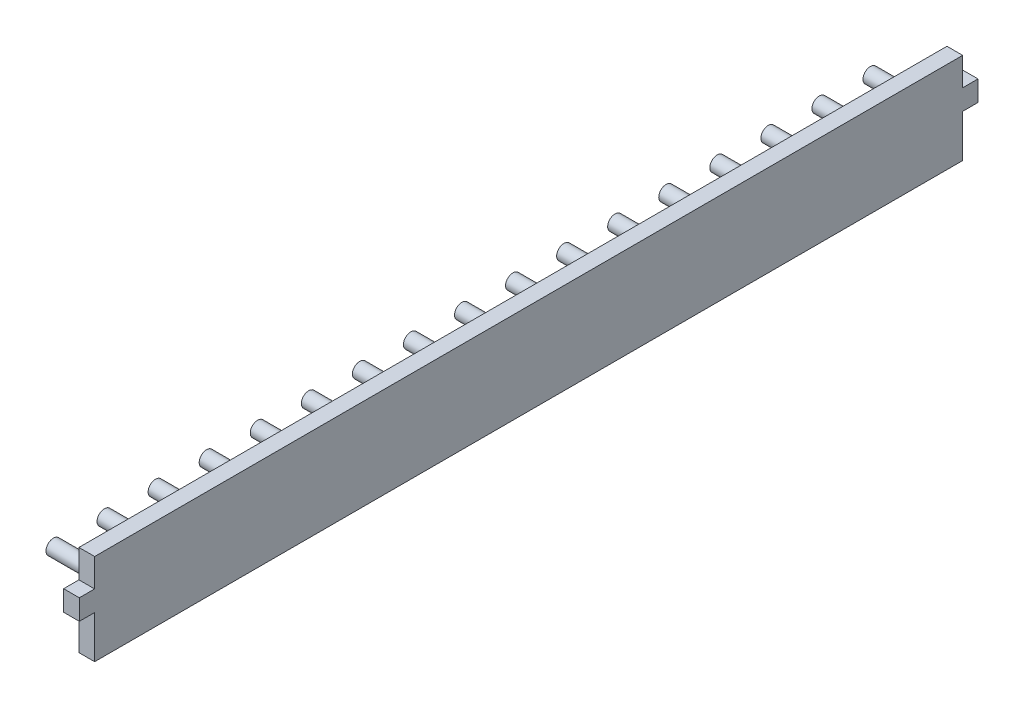
SolidWorks part; units mm, degrees
ref_plane "Front Plane" through (0, 0, 0) normal (0, 0, 1) x (1, 0, 0)
ref_plane "Top Plane" through (0, 0, 0) normal (0, 1, 0) x (1, 0, 0)
ref_plane "Right Plane" through (0, 0, 0) normal (1, 0, 0) x (0, 0, -1)
sketch "Sketch1" plane through (0, 0, 0) normal (0, 0, 1) x (1, 0, 0)
  line B0 (0, 7.95) -> (2.04, 7.95)
  line B1 (6.1524, 4.048) -> (6.1524, -4.048)
  line B2 (2.04, -7.95) -> (0, -7.95)
  line B3 (0, -7.95) -> (0, 7.95)
  line B4 (2.04, 7.95) -> (6.1524, 4.048)
  line B5 (6.1524, -4.048) -> (2.04, -7.95)
sketch_block_instance "Extrusion Profile-1"
sketch_block "Extrusion Profile" parameters "D1"=8.44, "D2"=2.6, "D3"=6, "D4"=16.7, "D6"=5.6686, "D7"=2.0404, "D8"=8.0963, "D9"=15.9, "D5"=2.4157
extrude "Boss-Extrude1" add sketch "Sketch1" along normal blind 340
sketch "Sketch2" plane through (0, 0, 0) normal (-1, 0, 0) x (0, 0, 1)
  circle A0 centre (10, 0) radius 2.9
  circle A1 centre (30, 0) radius 2.9
  circle A2 centre (50, 0) radius 2.9
  circle A3 centre (70, 0) radius 2.9
  circle A4 centre (90, 0) radius 2.9
  circle A5 centre (110, 0) radius 2.9
  circle A6 centre (130, 0) radius 2.9
  circle A7 centre (150, 0) radius 2.9
  circle A8 centre (170, 0) radius 2.9
  circle A9 centre (190, 0) radius 2.9
  circle A10 centre (210, 0) radius 2.9
  circle A11 centre (230, 0) radius 2.9
  circle A12 centre (250, 0) radius 2.9
  dimension "D2" = 5.8
  dimension "D1" = 10
  dimension "D4" = 20
  dimension "D3" = 13
extrude "Boss-Extrude2" add sketch "Sketch2" along normal blind 20
sketch "Sketch3" [suppressed] plane through (0, 0, 0) normal (-1, 0, 0) x (0, 0, 1)
  line L0 (190, 0) -> (210, 0) construction
  line L1 (200, 0) -> (200, 7.95) construction
  line L2 (260, 7.95) -> (0, 7.95) construction
  line L3 (200, 7.95) -> (200, 7)
  line L4 (200, 7) -> (100, 7)
  line L5 (100, 7) -> (100, 7.95)
  line L6 (100, 7.95) -> (200, 7.95)
  line L7 (90, 0) -> (110, 0) construction
  line L8 (100, 0) -> (100, 7) construction
  dimension "D1" = 7
extrude "Cut-Extrude1" [suppressed] cut sketch "Sketch3" against normal through all
chamfer "Chamfer1" [suppressed] distance 3 angle 45
fillet "Fillet1" [suppressed] radius 8
sketch "Sketch4" plane through (0, 0, 0) normal (-1, 0, 0) x (0, 0, 1)
  line L0 (250, 0) -> (230, 0) construction
  line L1 (250, 0) -> (270, 0) construction
  circle A0 centre (270, 0) radius 2.9
  circle A1 centre (250, 0) radius 2.9 construction
  circle A2 centre (290, 0) radius 2.9
  circle A3 centre (310, 0) radius 2.9
  circle A4 centre (330, 0) radius 2.9
  dimension "D2" = 20
  dimension "D1" = 4
extrude "Boss-Extrude3" add sketch "Sketch4" along normal blind 20
sketch "Sketch5" plane through (0, 0, 340) normal (0, 0, 1) x (1, 0, 0)
  line L5 (0, -7.95) -> (0, -20.95)
  line L6 (0, -20.95) -> (6.1524, -20.95)
  line L7 (6.1524, -20.95) -> (6.1524, -4.048)
  line L8 (0, -7.95) -> (2.04, -7.95) construction
  line L9 (0, -7.95) -> (2.04, -7.95)
  line L10 (2.04, -7.95) -> (6.1524, -4.048)
  line L11 (0, 7.95) -> (0, 14.75)
  line L12 (0, 14.75) -> (6.1524, 14.75)
  line L13 (6.1524, 14.75) -> (6.1524, 4.048)
  line L14 (2.04, 7.95) -> (0, 7.95) construction
  line L15 (0, 7.95) -> (2.04, 7.95)
  line L16 (2.04, 7.95) -> (6.1524, 4.048)
  dimension "D1" = 13
  dimension "D2" = 6.8
extrude "Boss-Extrude4" add sketch "Sketch5" against normal up to surface (340 mm away) up to face at (2.7308, 0, 0)
sketch "Sketch7" plane through (0, 0, 340) normal (0, 0, 1) x (1, 0, 0)
  line L0 (6.1524, -20.95) -> (6.1524, 14.75) construction
  line L1 (6.1524, -4.25) -> (0, -4.25)
  line L2 (6.1524, -4.25) -> (6.1524, 3.75)
  line L3 (6.1524, 3.75) -> (0, 3.75)
  line L4 (0, -4.25) -> (0, 3.75)
  line L5 (0, 14.75) -> (0, -20.95) construction
  line L6 (0, -0.25) -> (6.1524, -0.25)
  line L8 (6.1524, 14.75) -> (0, 14.75) construction
  line M7 (6.1524, -20.95) -> (6.1524, 14.75)
  line M9 (0, 14.75) -> (0, -20.95)
  dimension "D1" = 8
  dimension "D2" = 15
extrude "Boss-Extrude5" add sketch "Sketch7" along normal blind 6 contours L6 L2 L3 M9 | L6 L4 L1 M7 region at (3.0762, -2.25, 340) region at (3.0762, 1.75, 340)
ref_plane "Plane1" through (0, 0, 170) normal (0, 0, 1) x (1, 0, 0)
mirror "Mirror1" about plane through (0, 0, 170) normal (0, 0, 1) of "Boss-Extrude5"
